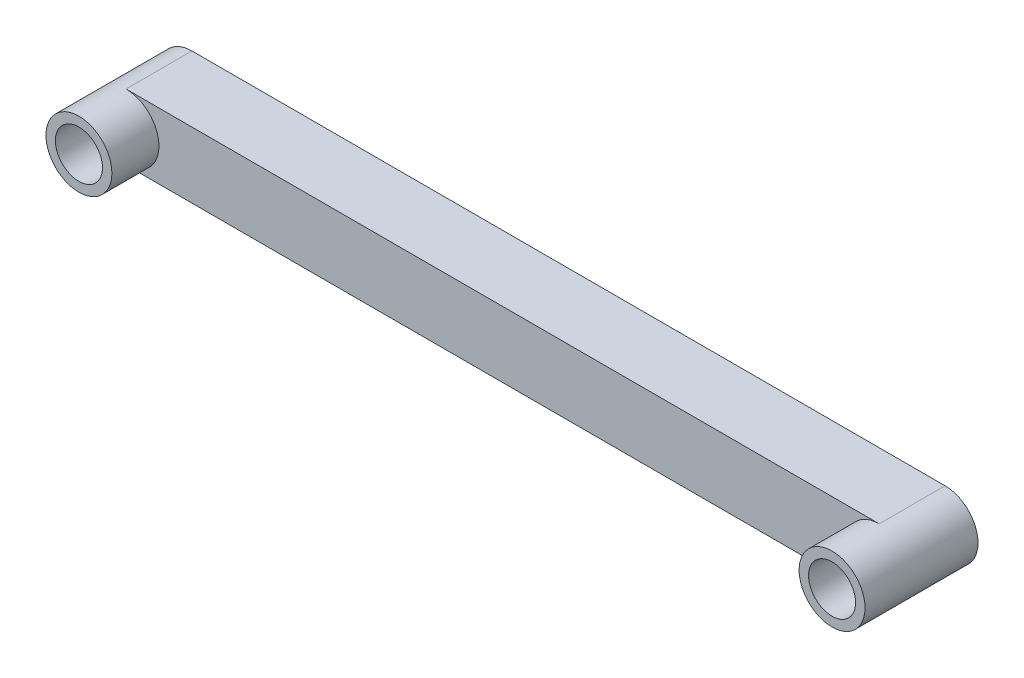
SolidWorks part; units mm, degrees
ref_plane "前视基准面" through (0, 0, 0) normal (0, 0, 1) x (1, 0, 0)
ref_plane "上视基准面" through (0, 0, 0) normal (0, 1, 0) x (1, 0, 0)
ref_plane "右视基准面" through (0, 0, 0) normal (1, 0, 0) x (0, 0, -1)
sketch "草图1" plane through (0, 0, 0) normal (0, 0, 1) x (1, 0, 0)
  line L0 (-46.5929, 0) -> (113.4071, 0) construction
  line L1 (-46.5929, 7) -> (113.4071, 7)
  line L2 (-46.5929, -7) -> (113.4071, -7)
  arc A0 (-46.5929, 7) -> (-46.5929, -7) centre (-46.5929, 0) ccw
  arc A1 (113.4071, -7) -> (113.4071, 7) centre (113.4071, 0) ccw
  circle A2 centre (-46.5929, 0) radius 7
  circle A3 centre (113.4071, 0) radius 7
  circle A4 centre (-46.5929, 0) radius 5
  circle A5 centre (113.4071, 0) radius 5
  point P3 (33.4071, 0)
  dimension "D1" = 7
  dimension "D3" = 10
  dimension "D4" = 10
  dimension "D2" = 160
extrude "凸台-拉伸2" add sketch "草图1" along normal blind 4 contours A4 | A2 L0 A3 L1 | L0 A2 L2 A3 | A5 region at (33.4071, 3.539, 0) region at (33.4071, -3.539, 0) region at (-51.4514, 0, 0) region at (113.4071, 4.8586, 0)
extrude "凸台-拉伸3" add sketch "草图1<4>" along normal blind 14 contours A4 A2 A0 | A1 A3 A5 region at (-41.7831, 4.8097, 0) region at (118.2169, 4.8097, 0)
sketch "草图1<4>" plane through (0, 0, 0) normal (0, 0, 1) x (1, 0, 0) same geometry as "草图1"
sketch "草图2" plane through (0, 0, 0) normal (0, 0, -1) x (-1, 0, 0)
  line L2 (46.5929, 7) -> (-113.4071, 7)
  line L6 (46.5929, 7) -> (-113.4071, 7)
  line L8 (-113.4071, -7) -> (46.5929, -7)
  line L9 (-113.4071, -7) -> (46.5929, -7)
  arc A2 (46.5929, -7) -> (46.5929, 7) centre (46.5929, 0) ccw
  arc A6 (46.5929, -7) -> (46.5929, 7) centre (46.5929, 0) ccw
  arc A8 (-113.4071, 7) -> (-113.4071, -7) centre (-113.4071, 0) ccw
  arc A9 (-113.4071, 7) -> (-113.4071, -7) centre (-113.4071, 0) ccw
  dimension "D1" = 0
extrude "凸台-拉伸4" add sketch "草图2" along normal blind 10
